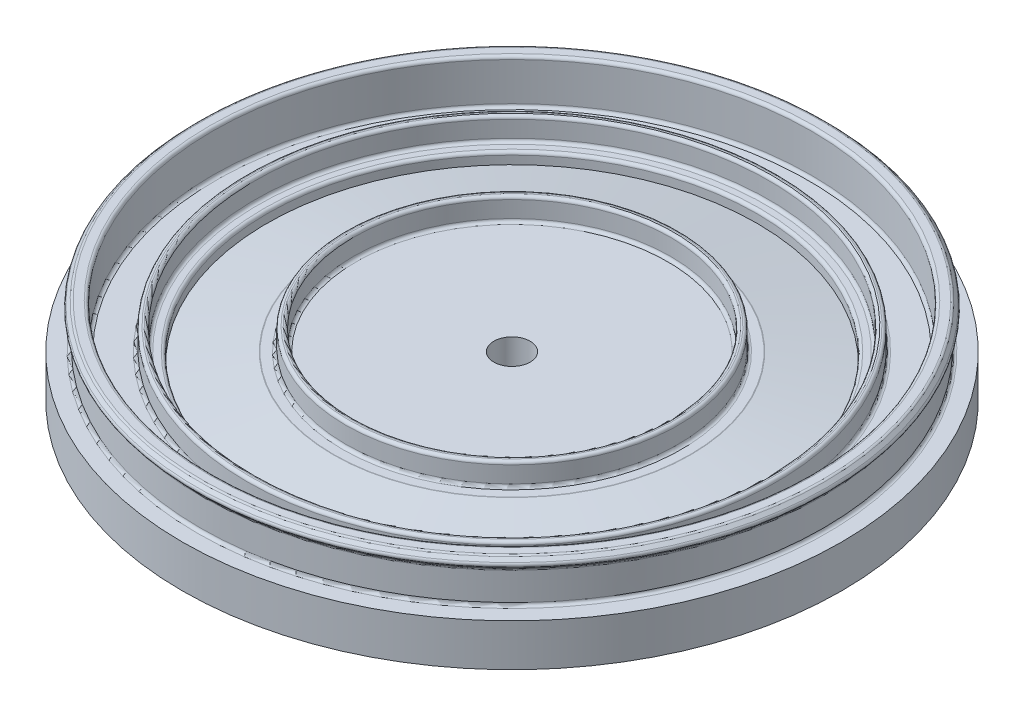
SolidWorks part; units mm, degrees
ref_plane "Front Plane" through (0, 0, 0) normal (0, 0, 1) x (1, 0, 0)
ref_plane "Top Plane" through (0, 0, 0) normal (0, 1, 0) x (1, 0, 0)
ref_plane "Right Plane" through (0, 0, 0) normal (1, 0, 0) x (0, 0, -1)
sketch "Sketch2" plane through (0, 0, 0) normal (0, 1, 0) x (1, 0, 0)
  circle A0 centre (0, 0) radius 54.5
  dimension "D1" = 109
extrude "Boss-Extrude1" add sketch "Sketch2" along normal blind 7
sketch "Sketch3" plane through (0, 0, 0) normal (0, 0, 1) x (1, 0, 0)
  line L0 (0, 0) -> (0, 7) construction
  line L1 (54.5, 7) -> (-54.5, 7) construction
  line L2 (0, 7) -> (-29.5, 7) construction
  line L3 (-29.5, 7) -> (-40.5, 7)
  line L4 (-40.5, 7) -> (-40.5, 5.127)
  line L5 (-40.5, 5.127) -> (-29.5, 7)
  dimension "D1" = 29.5
  dimension "D2" = 11
  dimension "D3" = 1.873
revolve "Cut-Revolve1" cut sketch "Sketch3" angle 360 about L0
sketch "Sketch4" plane through (0, 7, 0) normal (0, 1, 0) x (1, 0, 0)
  circle A0 centre (0, 0) radius 43.75
  circle A1 centre (0, 0) radius 42.5
  circle A2 centre (0, 0) radius 27.5
  circle A3 centre (0, 0) radius 26.25
  dimension "D1" = 87.5
  dimension "D2" = 85
  dimension "D3" = 55
  dimension "D4" = 52.5
extrude "Boss-Extrude2" add sketch "Sketch4" along normal blind 3.723 contours A0 A1 | A2 A3 region at (-42.5126, 7, 0) region at (-26.7222, 7, 0)
fillet "Fillet1" radius 0.5 10 edges at (0, 7, 26.25) (0, 7, -29.5) (0, 7, -40.5) (0, 10.723, 43.75) (0, 7, 42.5) (0, 10.723, 42.5) (0, 7, 27.5) (0, 10.723, 27.5) (0, 10.723, 26.25) (0, 7, 43.75)
sketch "Sketch5" plane through (0, 0, 0) normal (0, 0, 1) x (1, 0, 0)
  line L0 (0, 7) -> (-49.5, 7) construction
  line L1 (54.5, 7) -> (-54.5, 7) construction
  line L2 (0, 7) -> (0, 24.3916) construction
  line L3 (0, -55) -> (0, 55) construction
  line L4 (-49.5, 7) -> (-51.5, 7)
  line L5 (-51.5, 7) -> (-51.5, 12.323)
  line L6 (-51.5, 12.323) -> (-52.5, 13.323)
  line L7 (-52.5, 13.323) -> (-51.5, 14.323)
  line L8 (-51.5, 14.323) -> (-49.5, 14.323)
  line L9 (-49.5, 14.323) -> (-49.5, 7)
  point P15 (-39.1102, 10.2106)
  point P16 (-41.4318, 9.2397)
  dimension "D1" = 7.323
  dimension "D2" = 1
  dimension "D3" = 1
  dimension "D4" = 2
  dimension "D5" = 2
  dimension "D6" = 49.5
revolve "Revolve1" add sketch "Sketch5" angle 360 about L2
fillet "Fillet2" radius 0.5 6 edges at (51.5, 7, 0) (49.5, 7, 0) (49.5, 14.323, 0) (51.5, 14.323, 0) (51.5, 12.323, 0) (52.5, 13.323, 0)
sketch "Sketch6" plane through (0, 7, 0) normal (0, 1, 0) x (1, 0, 0)
  circle A0 centre (0, 0) radius 3
  dimension "D1" = 6
extrude "Cut-Extrude1" cut sketch "Sketch6" against normal blind 6
